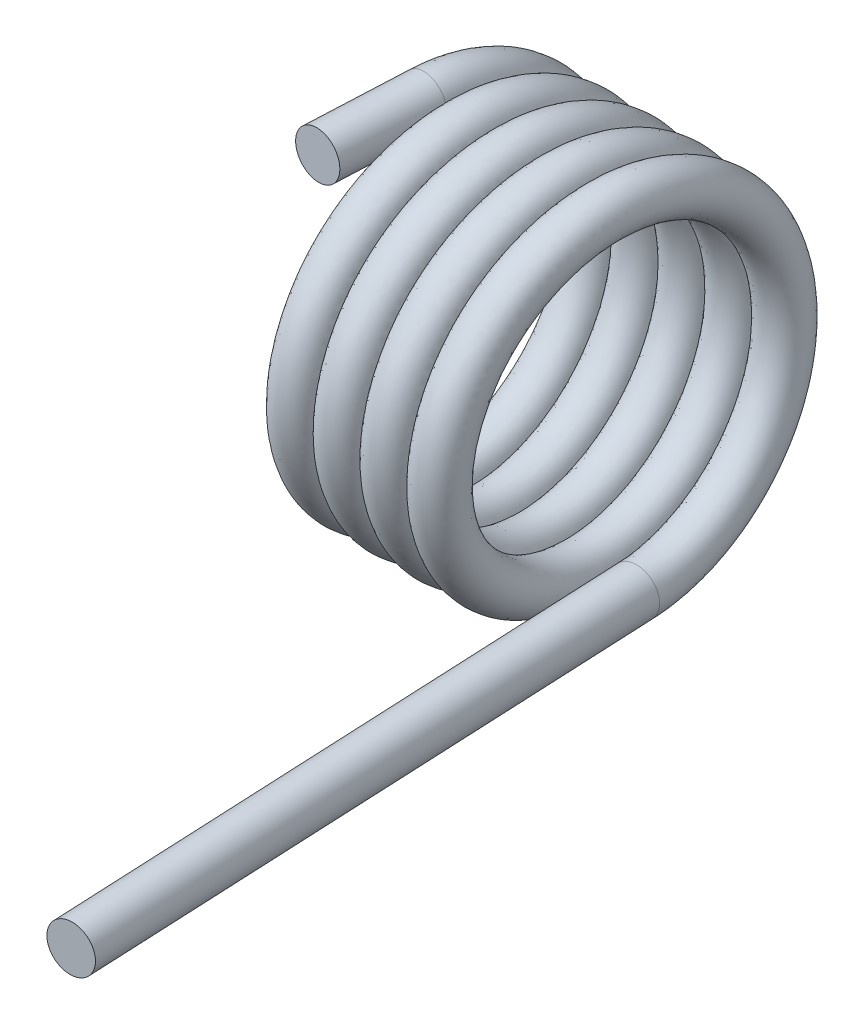
SolidWorks part; units mm, degrees
ref_plane "Front" through (0, 0, 0) normal (0, 0, 1) x (1, 0, 0)
ref_plane "Top" through (0, 0, 0) normal (0, 1, 0) x (1, 0, 0)
ref_plane "Right" through (0, 0, 0) normal (1, 0, 0) x (0, 0, -1)
sketch "Sketch1" plane through (0, 0, 0) normal (1, 0, 0) x (0, 0, -1)
  line L0 (0, -9.3853) -> (0, -12.5603) construction
  line L1 (12.5603, 0) -> (12.5603, 40.5) construction
  line L2 (0, -12.5603) -> (-40.5, -12.5603) construction
  line L3 (0, 0) -> (12.5603, 0) construction
  line L4 (0, 0) -> (12.5603, 0) construction
  line L5 (-40.5, -12.5603) -> (-40.5, -9.3853) construction
  line L6 (-40.5, -9.3853) -> (0, -9.3853) construction
  line L7 (12.5603, 40.5) -> (9.3853, 40.5) construction
  line L8 (9.3853, 40.5) -> (9.3853, 0) construction
  circle A0 centre (0, 0) radius 12.5603 construction
  circle A1 centre (0, 0) radius 7.5057 construction
  circle A2 centre (0, 0) radius 10.9728 construction
  point P7 (0, -10.9728)
  point P10 (0, 12.5603)
  dimension "OD" = 25.1206
  dimension "For Shaft Diameter" = 15.0114
  dimension "Wire Diameter" = 3.175
  dimension "Leg Length" = 40.5
  dimension "Deflection Angle" = 90
sketch "Sketch2" plane through (0, 0, 0) normal (1, 0, 0) x (0, 0, -1)
  circle A0 centre (0, 0) radius 10.9728 construction
  circle A2 centre (0, 0) radius 10.9728
curve "Helix/Spiral1" pitch 3.2004 height 14.4018 turns 4.5
ref_plane "Plane1" through (0, -10.9728, 0) normal (-0.0464, 0, -0.9989) x (0.9987, -0.0232, -0.0464)
sketch "Sketch3" plane through (0, -10.9728, 0) normal (-0.0464, 0, -0.9989) x (0.9987, -0.0232, -0.0464)
  circle A0 centre (0, 0) radius 1.5875
  dimension "D1" = 3.175
sweep "Sweep1" add profiles "Sketch3" path "Helix/Spiral1"
sketch "Sketch4" plane through (0, 0, 0) normal (0.0464, 0, 0.9989) x (-0.9987, 0.0232, 0.0464)
  circle A1 centre (-0.255, 10.9698) radius 1.5875
  circle A2 centre (-0.255, 10.9698) radius 1.5875
  dimension "D1" = 0
extrude "Extrude1" add sketch "Sketch4" along normal blind 40.5
sketch "Sketch5" plane through (-0.031, 0, 0.6671) normal (-0.0464, 0, 0.9989) x (0.9922, 0.116, 0.0461)
  circle A1 centre (-13.0159, 12.568) radius 1.5875
  circle A2 centre (-13.0159, 12.568) radius 1.5875
  dimension "D1" = 0
extrude "Extrude2" add sketch "Sketch5" along normal blind 7
sketch "Sketch6" plane through (0, 0, 0) normal (1, 0, 0) x (0, 0, -1)
  circle A2 centre (0, 0) radius 9.3853 construction
equation "\"D4@Helix/Spiral1\" = \"Wire Diameter@Sketch1\" + .001"
equation "\"D1@Sketch3\"=\"Wire Diameter@Sketch1\""
equation "\"Leg Length@Extrude1\"=\"Leg Length@Sketch1\""
